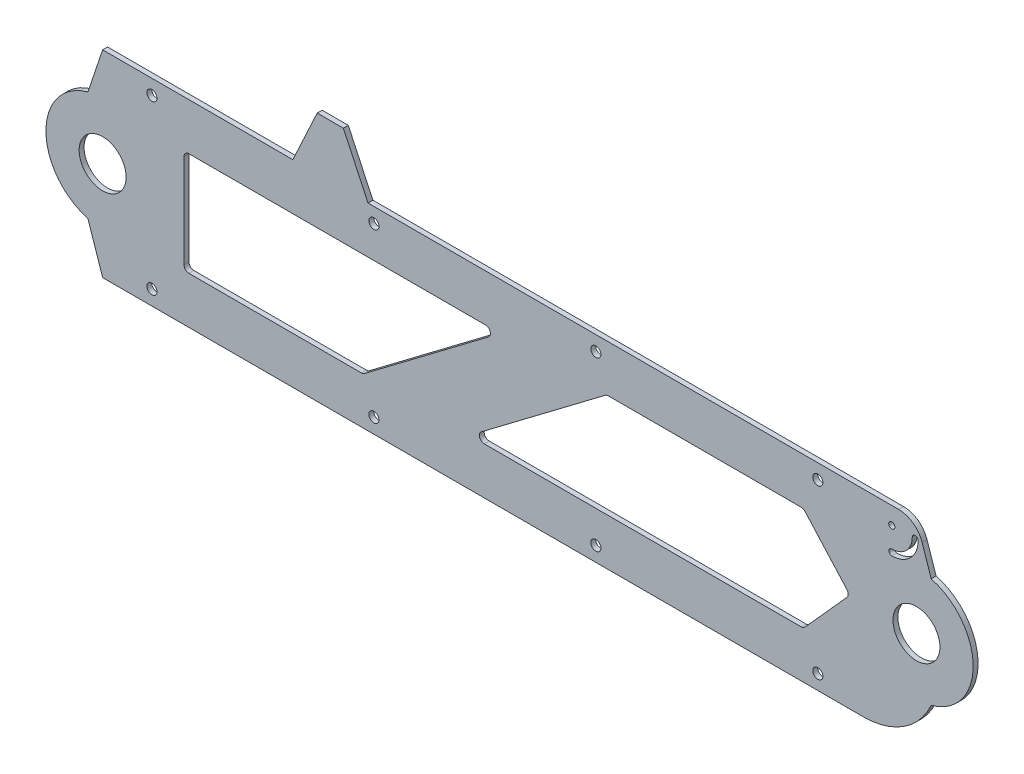
SolidWorks part; units mm, degrees
ref_plane "前视基准面" through (0, 0, 0) normal (0, 0, 1) x (1, 0, 0)
ref_plane "上视基准面" through (0, 0, 0) normal (0, 1, 0) x (1, 0, 0)
ref_plane "右视基准面" through (0, 0, 0) normal (1, 0, 0) x (0, 0, -1)
sketch "草图1" plane through (0, 0, 0) normal (0, 0, 1) x (1, 0, 0)
  line L0 (328.5429, -0.1457) -> (-1.4571, -0.1457) construction
  line L8 (328.5429, -40.1457) -> (-1.4571, -40.1457)
  line L9 (-1.4571, 39.8543) -> (328.5429, 39.8543) construction
  line L10 (328.5429, -0.1457) -> (340.7951, 45.5801) construction
  line L11 (328.5429, -0.1457) -> (340.7951, -45.8715) construction
  line L14 (334.4957, 22.0706) -> (328.5429, 39.8543)
  line L17 (334.4957, -22.362) -> (328.5429, -40.1457)
  line L18 (163.5429, -0.1457) -> (163.5429, 12.1844) construction
  line L19 (-1.4571, 39.8543) -> (-7.41, 22.0706)
  line L20 (-7.41, -22.362) -> (-1.4571, -40.1457)
  line L34 (96.1749, 61.1543) -> (106.1459, 39.8543)
  line L35 (96.1749, 61.1543) -> (85.5444, 61.1543)
  line L36 (85.5444, 61.1543) -> (75.6844, 39.8543)
  line L37 (75.6844, 39.8543) -> (-1.4571, 39.8543)
  line L38 (106.1459, 39.8543) -> (321.0716, 39.8543)
  line L41 (356.5429, 50.4301) -> (356.5429, 24.1217) construction
  line L42 (321.0716, 39.8543) -> (356.5429, 39.8543) construction
  line L44 (356.5429, 24.1217) -> (347.9586, 12.1844) construction
  line L45 (321.0716, 39.8543) -> (328.5429, 39.8543)
  circle A0 centre (-1.4571, -0.1457) radius 9.52
  circle A1 centre (-1.4571, -0.1457) radius 40 construction
  circle A11 centre (328.5429, -0.1457) radius 9.52
  circle A12 centre (328.5429, -0.1457) radius 40 construction
  circle A16 centre (328.5429, -0.1457) radius 23 construction
  circle A25 centre (318.5429, 32.8543) radius 1.25
  circle A26 centre (318.5429, 32.8543) radius 9.5 construction
  arc A27 (318.5429, 23.3543) -> (328.0429, 32.8543) centre (318.5429, 32.8543) ccw construction
  arc A37 (-7.41, -22.362) -> (-7.41, 22.0706) centre (-1.4571, -0.1457) cw
  arc A40 (334.4957, 22.0706) -> (334.4957, -22.362) centre (328.5429, -0.1457) cw
  arc A41 (318.5429, 22.1543) -> (329.2429, 32.8543) centre (318.5429, 32.8543) ccw
  arc A42 (318.5429, 24.5543) -> (326.8429, 32.8543) centre (318.5429, 32.8543) ccw
  arc A43 (318.5429, 24.5543) -> (318.5429, 22.1543) centre (318.5429, 23.3543) ccw
  arc A44 (329.2429, 32.8543) -> (326.8429, 32.8543) centre (328.0429, 32.8543) ccw
  point P10 (325.2604, 26.1368)
  dimension "D1" = 330
  dimension "D2" = 19.04
  dimension "D3" = 2.5
  dimension "D4" = 19.04
  dimension "D5" = 80
  dimension "D6" = 7
  dimension "D7" = 19
  dimension "D8" = 105
  dimension "D9" = 10
extrude "凸台-拉伸1" add sketch "草图1" along normal blind 2
sketch "草图2" plane through (0, 0, 2) normal (0, 0, 1) x (1, 0, 0)
  line L0 (198.5429, 33.8543) -> (288.5429, 33.8543) construction
  line L1 (18.5429, 33.8543) -> (198.5429, 33.8543) construction
  line L2 (108.5429, -34.1457) -> (198.5429, 33.8543) construction
  line L3 (18.5429, 33.8543) -> (18.5429, -34.1457) construction
  line L4 (18.5429, -34.1457) -> (108.5429, -34.1457) construction
  line L5 (31.5429, -21.1457) -> (104.1839, -21.1457)
  line L6 (104.1839, -21.1457) -> (159.7721, 20.8543)
  line L7 (31.5429, 20.8543) -> (159.7721, 20.8543)
  line L8 (31.5429, 20.8543) -> (31.5429, -21.1457)
  line L9 (108.5429, -34.1457) -> (288.5429, -34.1457) construction
  line L20 (288.5429, 33.8543) -> (319.0229, -0.1457) construction
  line L28 (147.3136, -21.1457) -> (202.9018, 20.8543)
  line L31 (319.0229, -0.1457) -> (288.5429, -34.1457) construction
  line L40 (202.9018, 20.8543) -> (282.7379, 20.8543)
  line L41 (282.7379, 20.8543) -> (301.5638, -0.1457)
  line L42 (301.5638, -0.1457) -> (282.7379, -21.1457)
  line L43 (18.5429, 33.8543) -> (-161.4571, 33.8543) construction
  line L54 (147.3136, -21.1457) -> (282.7379, -21.1457)
  circle A1 centre (108.5429, 33.8543) radius 2.05
  circle A2 centre (198.5429, 33.8543) radius 2.05
  circle A3 centre (288.5429, 33.8543) radius 2.05
  circle A4 centre (108.5429, -34.1457) radius 2.05
  circle A5 centre (198.5429, -34.1457) radius 2.05
  circle A6 centre (288.5429, -34.1457) radius 2.05
  circle A7 centre (18.5429, -34.1457) radius 2.05
  circle A10 centre (18.5429, 33.8543) radius 2.05
  circle A11 centre (328.5429, -0.1457) radius 9.52 construction
  point P2 (-1.4571, -0.1457)
  dimension "D1" = 13
  dimension "D2" = 34
  dimension "D6" = 13
extrude "切除-拉伸1" cut sketch "草图2" against normal blind 4
fillet "圆角1" radius 2 9 edges at (104.1839, -21.1457, 1) (159.7721, 20.8543, 1) (31.5429, -21.1457, 1) (31.5429, 20.8543, 1) (202.9018, 20.8543, 1) (282.7379, 20.8543, 1) (282.7379, -21.1457, 1) (301.5638, -0.1457, 1) (147.3136, -21.1457, 1)
fillet "圆角3" radius 30 1 edges at (328.5429, -40.1457, 1)
fillet "圆角6" radius 10 1 edges at (328.5429, 39.8543, 1)
